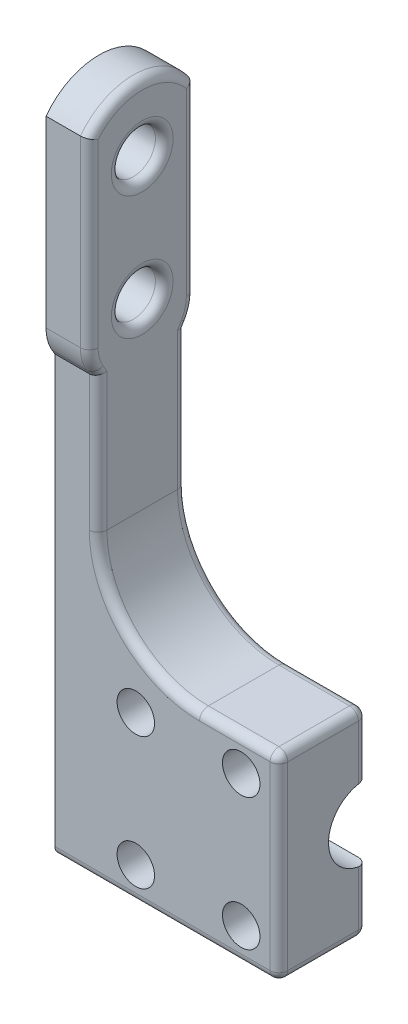
SolidWorks part; units mm, degrees
ref_plane "Front Plane" through (0, 0, 0) normal (0, 0, 1) x (1, 0, 0)
ref_plane "Top Plane" through (0, 0, 0) normal (0, 1, 0) x (1, 0, 0)
ref_plane "Right Plane" through (0, 0, 0) normal (1, 0, 0) x (0, 0, -1)
sketch "Sketch4" plane through (0, 0, 0) normal (0, 0, 1) x (1, 0, 0)
  line L0 (0, 0) -> (-11.95, -14.95) construction
  line L1 (-20.5, 22.5) -> (20.5, 22.5)
  line L2 (-20.5, 22.5) -> (-20.5, -22.5)
  line L3 (-20.5, -22.5) -> (20.5, -22.5)
  line L4 (20.5, 22.5) -> (20.5, -22.5)
  line L5 (0, 0) -> (11.95, -14.95) construction
  line L6 (0, 0) -> (11.95, 14.95) construction
  line L7 (-11.95, 14.95) -> (11.95, 14.95) construction
  line L8 (-11.95, 14.95) -> (-11.95, -14.95) construction
  line L9 (-11.95, -14.95) -> (11.95, -14.95) construction
  line L10 (11.95, 14.95) -> (11.95, -14.95) construction
  circle A4 centre (-11.95, 14.95) radius 4.25
  circle A5 centre (11.95, 14.95) radius 4.25
  circle A6 centre (11.95, -14.95) radius 4.25
  circle A7 centre (-11.95, -14.95) radius 4.25
  point P0 (0, 0)
  point P6 (0, 0)
  dimension "D3" = 8.5
  dimension "D4" = 23.9
  dimension "D1" = 41
  dimension "D2" = 45
  dimension "D5" = 29.9
extrude "Boss-Extrude1" add sketch "Sketch4" along normal blind 20
sketch "Sketch6" plane through (0, 0, 0) normal (0, 0, -1) x (-1, 0, 0)
  line L2 (20.5, -22.5) -> (20.5, 129.9)
  line L3 (20.5, 129.9) -> (30.3, 129.9)
  line L4 (30.3, 129.9) -> (30.3, -22.5)
  line L5 (30.3, -22.5) -> (20.5, -22.5)
  line L6 (-20.5, -22.5) -> (-20.5, 22.5) construction
  dimension "D1" = 50.8
  dimension "D2" = 152.4
extrude "Boss-Extrude2" add sketch "Sketch6" against normal blind 20
sketch "Sketch7" plane through (-20.5, 0, 0) normal (1, 0, 0) x (0, 0, -1)
  line L0 (-10, 129.9) -> (-10, 22.5) construction
  line L1 (-20, 129.9) -> (0, 129.9) construction
  line L2 (-20, 22.5) -> (0, 22.5) construction
  line L3 (0, 76.2) -> (0.5838, 77.1769)
  line L5 (0, 129.9) -> (0, 22.5) construction
  line L6 (2, 82.307) -> (2, 123.8853)
  line L7 (0.2383, 129.5537) -> (0, 129.9)
  line L8 (0, 76.2) -> (0, 129.9)
  line L9 (-20, 76.2) -> (-20.5838, 77.1769)
  line L10 (-22, 82.307) -> (-22, 123.8853)
  line L11 (-20.2383, 129.5537) -> (-20, 129.9)
  line L12 (-20, 76.2) -> (-20, 129.9)
  circle A0 centre (-10, 114.9) radius 5
  circle A1 centre (-10, 86.9) radius 5
  arc A2 (-20.5838, 77.1769) -> (-22, 82.307) centre (-12, 82.307) cw
  arc A3 (0.5838, 77.1769) -> (2, 82.307) centre (-8, 82.307) ccw
  arc A4 (2, 123.8853) -> (0.2383, 129.5537) centre (-8, 123.8853) ccw
  arc A5 (-22, 123.8853) -> (-20.2383, 129.5537) centre (-12, 123.8853) cw
  point P23 (-22, 79.5465)
  point P26 (2, 79.5465)
  point P29 (2, 126.9932)
  point P32 (-22, 126.9932)
  dimension "D1" = 28
  dimension "D2" = 10
  dimension "D4" = 10
  dimension "D5" = 15
  dimension "D3" = 12
extrude "Boss-Extrude3" add sketch "Sketch7" along direction (-1, 0, 0) on the side against the normal up to surface (9.8 mm away) up to face at (-30.3, 53.7, 10)
sketch "Sketch8" plane through (-20.5, 0, 0) normal (1, 0, 0) x (0, 0, -1)
  circle A1 centre (-10, 86.9) radius 5
  circle A2 centre (-10, 86.9) radius 5
  circle A3 centre (-10, 114.9) radius 5
  circle A4 centre (-10, 114.9) radius 5
  dimension "D1" = 0
  dimension "D2" = 0
extrude "Cut-Extrude2" cut sketch "Sketch8" against normal blind 15
sketch "Sketch5" plane through (20.5, 0, 0) normal (1, 0, 0) x (0, 0, -1)
  line L2 (0, -22.5) -> (0, 22.5) construction
  circle A0 centre (-0.5, 0) radius 8.25
  dimension "D1" = 16.5
  dimension "D2" = 0.5
extrude "Cut-Extrude1" cut sketch "Sketch5" against normal blind 65
sketch "Sketch9" plane through (0, 0, 0) normal (0, 0, -1) x (-1, 0, 0)
  line L4 (-2.5, 22.5) -> (20.5, 22.5)
  line L5 (20.5, 22.5) -> (20.5, 45.5)
  arc A0 (-2.5, 22.5) -> (20.5, 45.5) centre (-2.5, 45.5) ccw
  point P9 (20.5, 22.5)
  dimension "D1" = 23
extrude "Boss-Extrude4" add sketch "Sketch9" against normal up to surface (20 mm away) up to face at (-10.1, 25.4, 20)
ref_axis "Axis1" through (-30.3, 0, 0.5) along (1, 0, 0)
sketch "Sketch10" plane through (0, 0, 0) normal (0, 0, 1) x (1, 0, 0)
  line L0 (-30.3, -22.5) -> (-26.3, -22.5)
  line L1 (-30.3, -22.5) -> (-20.5, -22.5) construction
  line L2 (-26.3, -22.5) -> (-26.3, 157.5939)
  line L3 (-26.3, 157.5939) -> (-61.0758, 162.5234)
  line L4 (-61.0758, 162.5234) -> (-64.5228, 37.5847)
  line L5 (-64.5228, 37.5847) -> (-30.3, -22.5)
extrude "Cut-Extrude3" cut sketch "Sketch10" along normal blind 86 and the other way blind 86
sketch "Sketch11" plane through (-26.3, 0, 0) normal (-1, 0, 0) x (0, 0, 1)
  line L0 (0, -8.2348) -> (0, 8.2348)
  arc A0 (0, -8.2348) -> (0, 8.2348) centre (0.5, 0) ccw construction
  arc A1 (0, -8.2348) -> (0, 8.2348) centre (0.5, 0) ccw
extrude "Boss-Extrude5" add sketch "Sketch11" against normal blind 1.5
sketch "Sketch12" plane through (-20.5, 0, 0) normal (1, 0, 0) x (0, 0, -1)
  line L0 (-22, 123.8853) -> (-30.8203, 123.8853)
  line L1 (-30.8203, 123.8853) -> (-25.069, 136.8187)
  line L2 (-25.069, 136.8187) -> (-2.4795, 134.9128)
  line L3 (-2.4795, 134.9128) -> (8.9971, 125.2643)
  line L4 (8.9971, 125.2643) -> (2, 123.8853)
  arc A0 (-22, 123.8853) -> (2, 123.8853) centre (-10, 114.922) cw
extrude "Cut-Extrude4" cut sketch "Sketch12" against normal blind 13.5
fillet "Fillet1" radius 2 5 edges at (20.5, 0, 20) (-2.9, -22.5, 20) (-2.9, -22.5, 0) (20.5, -22.5, 10) (20.5, 22.5, 10)
fillet "Fillet2" radius 2 18 edges at (20.5, 14.3674, 0) (19.9142, 21.9142, 0) (10.5, 22.5, 0) (-13.7635, 29.2365, 0) (19.9142, 21.9142, 19.4142) (10.5, 22.5, 20) (-13.7635, 29.2365, 20) (-20.5, 103.0961, -2) (-20.5, 79.646, -1.6395) (-20.5, 76.6885, -0.2919) (-20.5, 60.85, 0) (-20.5, 60.85, 20) (-20.5, 76.6885, 20.2919) (-20.5, 79.646, 21.6395) (-20.5, 103.0961, 22) (-20.5, 129.9, 10) (-20.5, 114.9, 5) (-20.5, 86.9, 5)
fillet "Fillet4" radius 2 2 edges at (19.9142, -21.9142, 0.5858) (20.5, -14.3674, 0)
sketch "Sketch13" plane through (-26.3, 0, 0) normal (-1, 0, 0) x (0, 0, 1)
  line L7 (2, -22.5) -> (18, -22.5)
  line L8 (20, -20.5) -> (20, 76.2)
  line L9 (20, 76.2) -> (20.5838, 77.1769)
  line L10 (22, 82.307) -> (22, 123.8853)
  line L11 (-2, 123.8853) -> (-2, 82.307)
  line L12 (-0.5838, 77.1769) -> (0, 76.2)
  line L13 (0, 76.2) -> (0, -20.5)
  line L14 (2, -22.5) -> (18, -22.5)
  line L15 (20, -20.5) -> (20, 76.2)
  line L16 (20, 76.2) -> (20.5838, 77.1769)
  line L17 (22, 82.307) -> (22, 123.8853)
  line L18 (-2, 123.8853) -> (-2, 82.307)
  line L19 (-0.5838, 77.1769) -> (0, 76.2)
  line L20 (0, 76.2) -> (0, -20.5)
  circle A0 centre (10, 114.9) radius 5 construction
  circle A1 centre (10, 86.9) radius 5 construction
  circle A2 centre (10, 114.9) radius 5
  circle A3 centre (10, 86.9) radius 5
  arc A5 (18, -22.5) -> (20, -20.5) centre (18, -20.5) ccw
  arc A6 (20.5838, 77.1769) -> (22, 82.307) centre (12, 82.307) ccw
  arc A7 (22, 123.8853) -> (-2, 123.8853) centre (10, 114.922) ccw
  arc A8 (-2, 82.307) -> (-0.5838, 77.1769) centre (8, 82.307) ccw
  arc A9 (0, -20.5) -> (2, -22.5) centre (2, -20.5) ccw
  arc A10 (18, -22.5) -> (20, -20.5) centre (18, -20.5) ccw
  arc A11 (20.5838, 77.1769) -> (22, 82.307) centre (12, 82.307) ccw
  arc A12 (22, 123.8853) -> (-2, 123.8853) centre (10, 114.922) ccw
  arc A13 (-2, 82.307) -> (-0.5838, 77.1769) centre (8, 82.307) ccw
  arc A14 (0, -20.5) -> (2, -22.5) centre (2, -20.5) ccw
  dimension "D1" = 0
extrude "Boss-Extrude6" add sketch "Sketch13" along normal blind 4
sketch "Sketch14" plane through (-30.3, 0, 0) normal (-1, 0, 0) x (0, 0, 1)
  circle A0 centre (0, 0) radius 4
extrude "Cut-Extrude5" cut sketch "Sketch14" against normal blind 10
